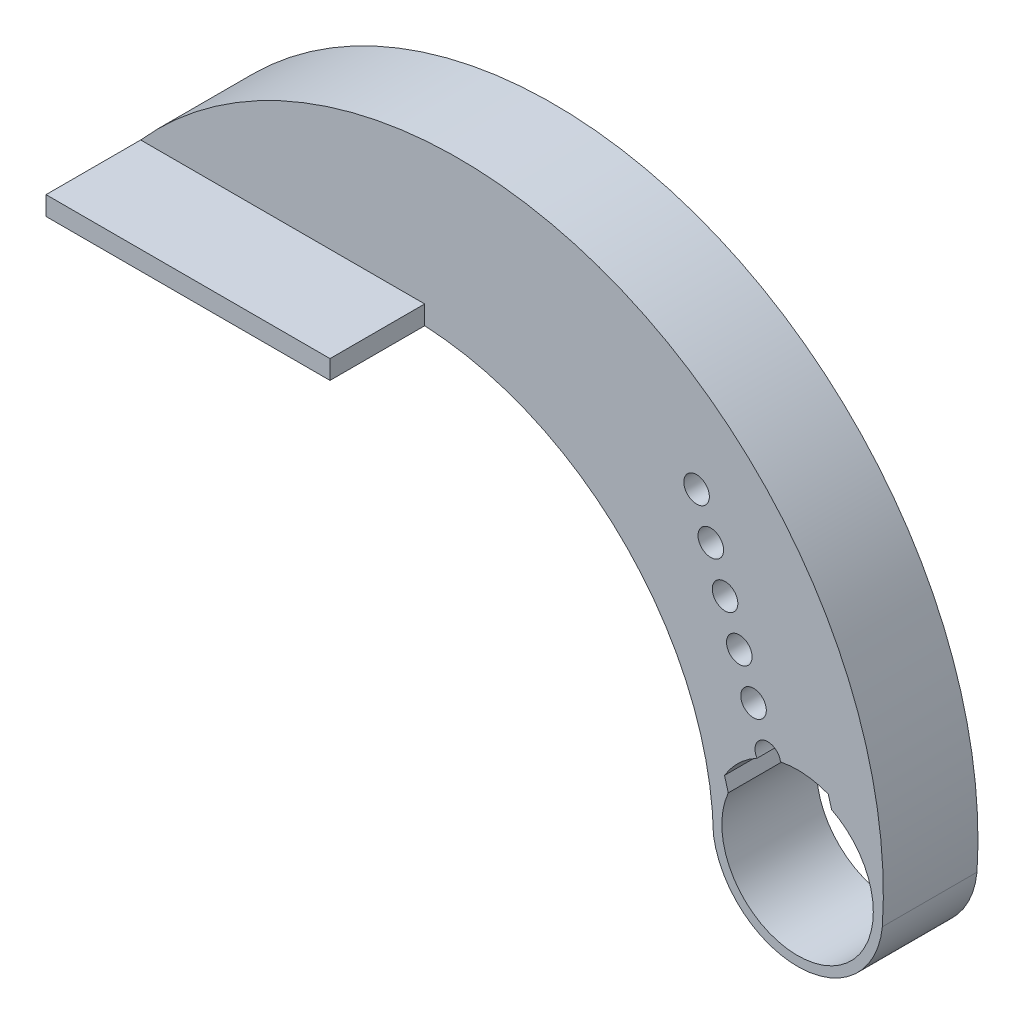
SolidWorks part; units mm, degrees
note: The reader was unsure of these and kept them because the rebuilt part matched: shared geometry of "Sketch1<3>", "Sketch1<4>".
ref_plane "Front Plane" through (0, 0, 0) normal (0, 0, 1) x (1, 0, 0)
ref_plane "Top Plane" through (0, 0, 0) normal (0, 1, 0) x (1, 0, 0)
ref_plane "Right Plane" through (0, 0, 0) normal (1, 0, 0) x (0, 0, -1)
sketch "Sketch1" plane through (0, 0, 0) normal (0, 0, 1) x (1, 0, 0)
  line L0 (-34.6968, 15.9601) -> (-19.6968, 15.9601)
  line L1 (1.1886, 4.2606) -> (-3.4561, 15.3432)
  line L3 (-34.6968, 15.9601) -> (-34.6968, 14.9601)
  line L4 (-34.6968, 14.9601) -> (-19.6968, 14.9601)
  line L5 (-19.6968, 15.9601) -> (-19.6968, 14.9601)
  line L6 (-7.2149, 13.9752) -> (-3.5101, 2.5504)
  line L7 (-3.5101, 2.5504) -> (-3.2353, 1.5789)
  line L8 (1.4634, 3.2891) -> (1.1886, 4.2606)
  line L9 (-5.3355, 14.6592) -> (0, 0) construction
  line L10 (-7.2149, 13.9752) -> (-3.4561, 15.3432) construction
  line L11 (-3.2353, 1.5789) -> (1.4634, 3.2891) construction
  line L12 (1.5669, 4.3929) -> (-3.0837, 15.4894)
  line L13 (-7.5933, 13.8453) -> (-3.8929, 2.4343)
  line L14 (-3.8929, 2.4343) -> (-3.6605, 1.6127)
  line L15 (1.7989, 3.5726) -> (1.5669, 4.3929)
  circle A2 centre (0, 0) radius 4.5
  arc A3 (-19.6968, 14.9601) -> (-4.4423, -0.7185) centre (-20.4642, -1.0469) cw
  arc A4 (-34.6968, 15.9601) -> (4.478, -0.4442) centre (-17.906, 1.0795) cw
  arc A5 (-3.4561, 15.3432) -> (-7.2149, 13.9752) centre (-5.3355, 14.6592) ccw
  arc A6 (-3.2353, 1.5789) -> (1.4634, 3.2891) centre (0, 0) ccw
  circle A7 centre (0, 0) radius 2.5
  circle A8 centre (-5.3355, 14.6592) radius 0.675
  circle A9 centre (-4.5831, 12.5919) radius 0.675
  circle A10 centre (-3.8306, 10.5246) radius 0.675
  circle A11 centre (-3.0782, 8.4572) radius 0.675
  circle A12 centre (-2.3257, 6.3899) radius 0.675
  circle A13 centre (-1.5733, 4.3226) radius 0.675
  arc A14 (-3.0837, 15.4894) -> (-7.5933, 13.8453) centre (-5.3355, 14.6592) ccw
  arc A15 (-3.6605, 1.6127) -> (1.7989, 3.5726) centre (0, 0) ccw
  dimension "D6" = 1
  dimension "D7" = 5
  dimension "D8" = 3.6
  dimension "D13" = 2
  dimension "D4" = 9
  dimension "D3" = 15
  dimension "D5" = 0.4
  dimension "D9" = 1.0096
  dimension "D10" = 1.0096
  dimension "D11" = 12.0104
  dimension "D12" = 20
  dimension "D14" = 15.6
  dimension "D15" = 4.772
  dimension "D16" = 2.2
  dimension "D17" = 2.2
  dimension "D18" = 2.2
  dimension "D19" = 2.2
  dimension "D20" = 2.2
extrude "Boss-Extrude1" add sketch "Sketch1" along normal blind 5
extrude "Boss-Extrude2" add sketch "Sketch1<3>" along normal blind 10 contours L5 L0 L3 L4
sketch "Sketch1<3>" plane through (0, 0, 0) normal (0, 0, 1) x (1, 0, 0) same geometry as "Sketch1"
extrude "Boss-Extrude3" add sketch "Sketch1<4>" against normal blind 2.5 from surface at 5 contours A13 A2 L8 L1 A5 L6 L7 A12 A11 A10 A9 A8 | L12 A14 L13 L14 A2 L7 L6 A5 L1 L8 L15
sketch "Sketch1<4>" plane through (0, 0, 0) normal (0, 0, 1) x (1, 0, 0) same geometry as "Sketch1"
